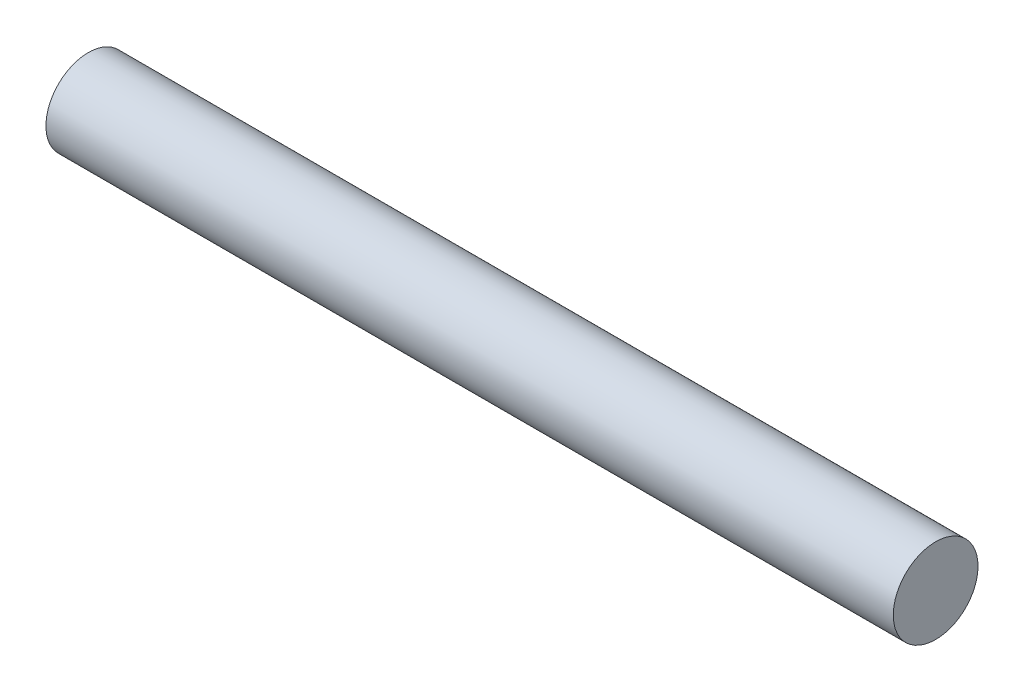
SolidWorks part; units mm, degrees
ref_plane "Front Plane" through (0, 0, 0) normal (0, 0, 1) x (1, 0, 0)
ref_plane "Top Plane" through (0, 0, 0) normal (0, 1, 0) x (1, 0, 0)
ref_plane "Right Plane" through (0, 0, 0) normal (1, 0, 0) x (0, 0, -1)
other "Default"
sketch "Sketch1" plane through (0, 0, 0) normal (1, 0, 0) x (0, 0, -1)
  circle A0 centre (0, 0) radius 2.5
  dimension "D1" = 5
extrude "Boss-Extrude1" add sketch "Sketch1" along normal mid plane 50
